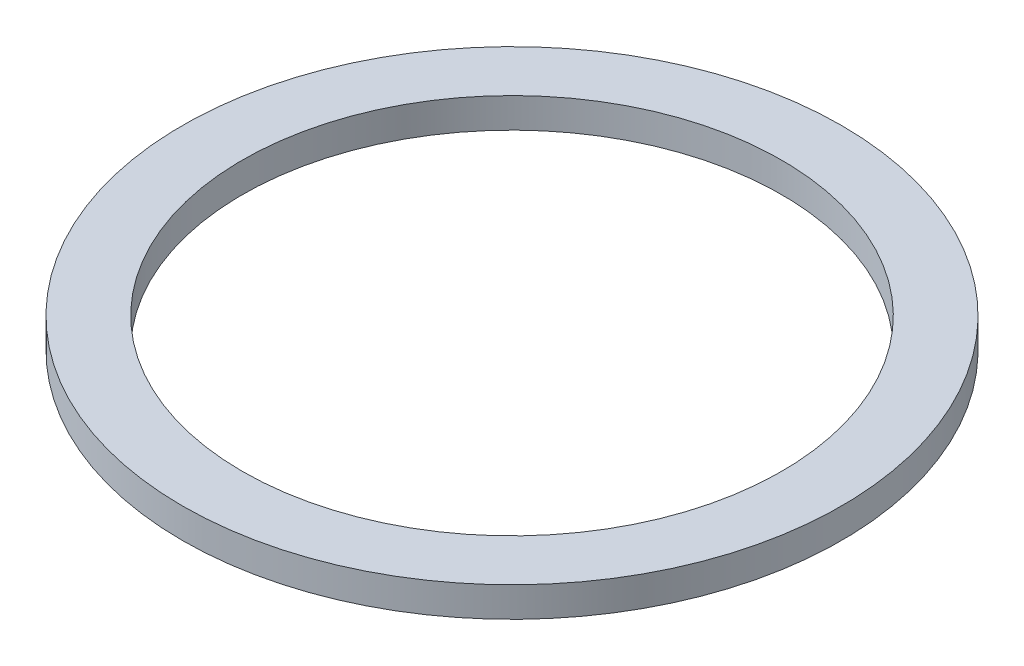
SolidWorks part; units mm, degrees
ref_plane "Front Plane" through (0, 0, 0) normal (0, 0, 1) x (1, 0, 0)
ref_plane "Top Plane" through (0, 0, 0) normal (0, 1, 0) x (1, 0, 0)
ref_plane "Right Plane" through (0, 0, 0) normal (1, 0, 0) x (0, 0, -1)
sketch "Sketch1" plane through (0, 0, 0) normal (0, 1, 0) x (1, 0, 0)
  circle A0 centre (0, 0) radius 55
  dimension "FLANGE_OD" = 110
extrude "Boss-Extrude1" add sketch "Sketch1" along normal blind 5
sketch "Sketch2" plane through (0, 0, 0) normal (0, 1, 0) x (1, 0, 0)
  circle A0 centre (0, 0) radius 45
  dimension "BORE_D" = 90
extrude "Cut-Extrude1" cut sketch "Sketch2" along normal through all
sketch "Sketch3" plane through (0, 5, 0) normal (0, 1, 0) x (1, 0, 0)
  circle A0 centre (0, 0) radius 24.948 construction
  circle A1 centre (-24.948, 0) radius 1.7169
  dimension "BOLT_D" = 3.4339
  dimension "BOLT_PCD" = 49.896
extrude "Cut-Extrude2" cut sketch "Sketch3" against normal blind 4.9301 rebuild error yes
pattern_circular "CirPattern1" count 3 over 360 rebuild error yes
